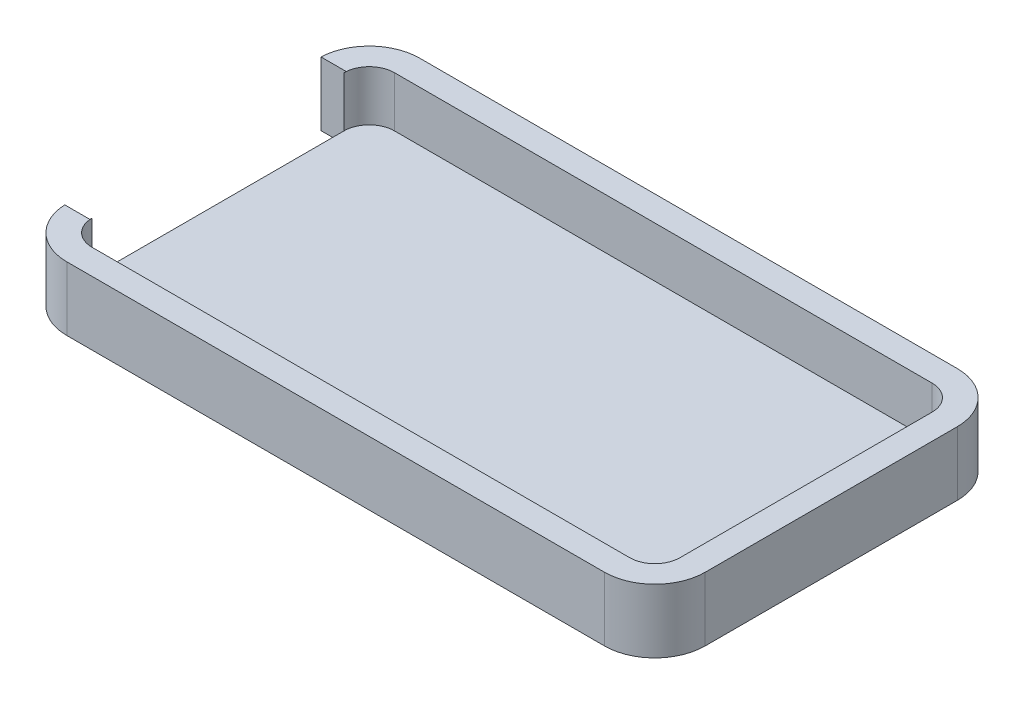
SolidWorks part; units mm, degrees
ref_plane "前视基准面" through (0, 0, 0) normal (0, 0, 1) x (1, 0, 0)
ref_plane "上视基准面" through (0, 0, 0) normal (0, 1, 0) x (1, 0, 0)
ref_plane "右视基准面" through (0, 0, 0) normal (1, 0, 0) x (0, 0, -1)
sketch "草图1" plane through (0, 0, 0) normal (0, 1, 0) x (1, 0, 0)
  line L0 (-16, 10.5) -> (16, 10.5)
  line L1 (-16, 9) -> (16, 9)
  line L2 (-17.5, 7.5) -> (-17.5, -7.5)
  line L3 (-16, -9) -> (16, -9)
  line L4 (17.5, 7.5) -> (17.5, -7.5)
  line L5 (-17.5, 9) -> (17.5, -9) construction
  line L6 (-17.5, -9) -> (17.5, 9) construction
  line L7 (19, 7.5) -> (19, -7.5)
  line L8 (-16, -10.5) -> (16, -10.5)
  line L9 (-19, 7.5) -> (-19, -7.5)
  line L10 (-18.186, 7.6661) -> (16.814, -10.3339)
  line L11 (-16.814, -10.3339) -> (18.186, 7.6661)
  arc A0 (-17.5, -7.5) -> (-16, -9) centre (-16, -7.5) ccw
  arc A1 (16, -9) -> (17.5, -7.5) centre (16, -7.5) ccw
  arc A2 (17.5, 7.5) -> (16, 9) centre (16, 7.5) ccw
  arc A3 (-16, 9) -> (-17.5, 7.5) centre (-16, 7.5) ccw
  arc A4 (19, 7.5) -> (16, 10.5) centre (16, 7.5) ccw
  arc A5 (16, -10.5) -> (19, -7.5) centre (16, -7.5) ccw
  arc A6 (-19, -7.5) -> (-16, -10.5) centre (-16, -7.5) ccw
  arc A7 (-16, 10.5) -> (-19, 7.5) centre (-16, 7.5) ccw
  point P0 (0, 0)
  dimension "D3" = 1.5
  dimension "D1" = 35
  dimension "D2" = 18
  dimension "D4" = 1.5
extrude "凸台-拉伸3" add sketch "草图1" along normal blind 3 contours L0 A7 L9 A6 L8 A5 L7 A4 A3 L1 A2 L4 A1 L3 A0 L2 region at (0, 0, -10.0658)
sketch "草图3" plane through (0, 0, 0) normal (0, -1, 0) x (1, 0, 0)
  line L0 (-16, 10.5) -> (16, 10.5) construction
  line L1 (-16, 10.5) -> (16, 10.5)
  line L2 (-19, -7.5) -> (-19, 7.5) construction
  line L3 (-16, -10.5) -> (16, -10.5) construction
  line L4 (19, -7.5) -> (19, 7.5) construction
  line L5 (-19, -7.5) -> (-19, 7.5)
  line L6 (-16, -10.5) -> (16, -10.5)
  line L7 (19, -7.5) -> (19, 7.5)
  arc A0 (-16, 10.5) -> (-19, 7.5) centre (-16, 7.5) ccw construction
  arc A1 (-16, 10.5) -> (-19, 7.5) centre (-16, 7.5) ccw
  arc A2 (-19, -7.5) -> (-16, -10.5) centre (-16, -7.5) ccw construction
  arc A3 (16, -10.5) -> (19, -7.5) centre (16, -7.5) ccw construction
  arc A4 (19, 7.5) -> (16, 10.5) centre (16, 7.5) ccw construction
  arc A5 (-19, -7.5) -> (-16, -10.5) centre (-16, -7.5) ccw
  arc A6 (16, -10.5) -> (19, -7.5) centre (16, -7.5) ccw
  arc A7 (19, 7.5) -> (16, 10.5) centre (16, 7.5) ccw
extrude "凸台-拉伸4" add sketch "草图3" along normal blind 0.8
sketch "草图4" plane through (0, 3, 0) normal (0, 1, 0) x (1, 0, 0)
  line L0 (-23.2798, 0) -> (26.7521, 0) construction
  line L1 (-17.5, 7.625) -> (-20.5, 7.625)
  line L3 (-17.5, 7.5) -> (-17.5, -7.5) construction
  line L4 (-20.5, 7.625) -> (-20.5, -7.625)
  line L5 (-20.5, -7.625) -> (-17.5, -7.625)
  line L6 (-17.5, -7.625) -> (-17.5, 7.625)
  dimension "D1" = 15.25
  dimension "D2" = 3
extrude "切除-拉伸1" cut sketch "草图4" against normal blind 4
